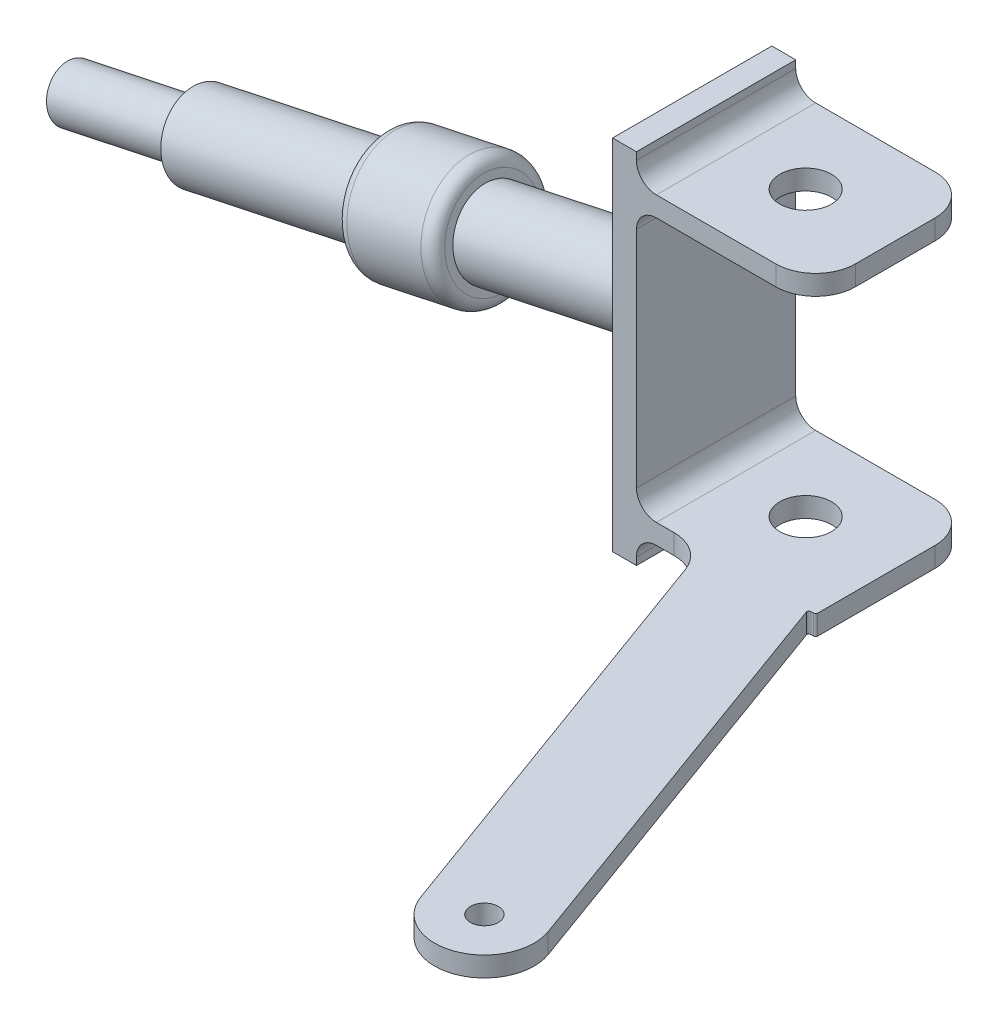
SolidWorks part; units mm, degrees
ref_plane "Front Plane" through (0, 0, 0) normal (0, 0, 1) x (1, 0, 0)
ref_plane "Top Plane" through (0, 0, 0) normal (0, 1, 0) x (1, 0, 0)
ref_plane "Right Plane" through (0, 0, 0) normal (1, 0, 0) x (0, 0, -1)
sketch "Sketch1" plane through (0, 0, 0) normal (1, 0, 0) x (0, 0, -1)
  line L1 (-20, 45) -> (20, 45)
  line L2 (-20, 45) -> (-20, -45)
  line L3 (-20, -45) -> (20, -45)
  line L4 (20, 45) -> (20, -45)
  line L5 (-20, 45) -> (20, -45) construction
  line L6 (-20, -45) -> (20, 45) construction
  point P0 (0, 0)
extrude "Boss-Extrude1" add sketch "Sketch1" along normal blind 6
sketch "Sketch2" plane through (6, 0, 0) normal (1, 0, 0) x (0, 0, -1)
  line L0 (20, -45) -> (20, 45) construction
  line L1 (-20, 33.1131) -> (20, 33.1131)
  line L2 (-20, 38.1131) -> (20, 38.1131)
  line L3 (-20, -33.1131) -> (20, -33.1131)
  line L4 (-20, -38.1131) -> (20, -38.1131)
  line L5 (-20, 33.1131) -> (20, -33.1131) construction
  line L6 (-20, -33.1131) -> (20, 33.1131) construction
  line L7 (-20, 38.1131) -> (-20, 33.1131)
  line L8 (20, 38.1131) -> (20, 33.1131)
  line L9 (20, -33.1131) -> (20, -38.1131)
  line L10 (-20, -38.1131) -> (-20, -33.1131)
  point P0 (0, 0)
extrude "Boss-Extrude2" add sketch "Sketch2" along normal blind 45
sketch "Sketch3" plane through (0, 38.1131, 0) normal (0, 1, 0) x (1, 0, 0)
  line L0 (6, 20) -> (51, -20) construction
  circle A0 centre (28.5, 0) radius 6.5
  dimension "D1" = 13
extrude "Cut-Extrude1" cut sketch "Sketch3" against normal through all
sketch "Sketch6" plane through (0, -33.1131, 0) normal (0, 1, 0) x (1, 0, 0)
  line L0 (28.5, 20) -> (28.5, -20) construction
  line L1 (51, 20) -> (6, 20) construction
  line L2 (51, -20) -> (6, -20) construction
  line L3 (6, -20) -> (51, -20)
  line L4 (22.4772, -20) -> (62.9266, -131.1338)
  line L5 (49.0816, -20) -> (86.4189, -122.5833)
  circle A0 centre (74.6727, -126.8585) radius 3.5
  arc A1 (62.9266, -131.1338) -> (86.4189, -122.5833) centre (74.6727, -126.8585) ccw
  line M3 (6, -20) -> (51, -20)
extrude "Boss-Extrude3" add sketch "Sketch6" against normal blind 5 contours L4 A1 L5 L3 A0 M3
sketch "Sketch7" plane through (0, 0, 0) normal (-1, 0, 0) x (0, 0, 1)
  line L0 (-20, 0) -> (20, 0) construction
  line L1 (-20, -45) -> (-20, 45) construction
  line L2 (20, 45) -> (20, -45) construction
ref_plane "Plane2" through (0, 0, 0) normal (0.9781, 0.2079, 0) x (0, 0, 1)
ref_plane "Plane3" through (0, 0, 0) normal (-0.2079, 0.9781, 0) x (0, 0, 1)
sketch "Sketch12" plane through (0, 0, 0) normal (0.9781, 0.2079, 0) x (0, 0, 1)
  circle A0 centre (0, 0) radius 10
  dimension "D1" = 20
sketch "Sketch16" plane through (0, 0, 0) normal (-0.2079, 0.9781, 0) x (0, 0, 1)
  line L0 (0, 0) -> (0, -126)
  line L1 (-20, 9.356) -> (20, 9.356) construction
  dimension "D1" = 126
sweep "Sweep3" add profiles "Sketch12" path "Sketch16"
ref_plane "Plane6" through (-49.8855, -10.6035, 0) normal (0.9781, 0.2079, 0) x (0, 0, 1)
sketch "Sketch19" plane through (-123.2466, -26.1969, 0) normal (-0.9781, -0.2079, 0) x (0, 0, 1)
  circle A0 centre (0, 0) radius 6.5
  dimension "D1" = 13
extrude "Boss-Extrude5" add sketch "Sketch19" along normal blind 33
sketch "Sketch20" plane through (-49.8855, -10.6035, 0) normal (0.9781, 0.2079, 0) x (0, 0, 1)
  circle A0 centre (0, 0) radius 15
  dimension "D1" = 30
extrude "Boss-Extrude6" add sketch "Sketch20" against normal blind 25
fillet "Fillet1" radius 10 1 edges at (51, 35.6131, -20)
fillet "Fillet2" radius 10 1 edges at (51, 35.6131, 20)
fillet "Fillet3" radius 10 3 edges at (51, -35.6131, -20)
fillet "Fillet4" radius 10 5 edges
fillet "Fillet5" radius 5 2 edges at (6, 38.1131, 0)
fillet "Fillet6" radius 5 2 edges at (6, 33.1131, 0)
fillet "Fillet7" radius 5 2 edges
fillet "Fillet8" radius 5 2 edges
fillet "Fillet9" radius 0.5 3 edges
fillet "Fillet10" radius 0.5 3 edges at (51, -35.6131, 20)
sketch "Sketch21" plane through (0, 0, 0) normal (-1, 0, 0) x (0, 0, 1)
  circle A0 centre (0, 0) radius 10
  dimension "D1" = 20
fillet "Fillet11" radius 3 2 edges at (-53.0042, 4.0687, 0) (-77.4579, -1.1291, 0)
sketch "Sketch24" plane through (0, 0, 0) normal (0.9781, 0.2079, 0) x (0, 0, 1)
  circle A0 centre (0, 0) radius 10
  dimension "D1" = 20
extrude "Boss-Extrude8" add sketch "Sketch24" along normal blind 3 contours A0
fillet "Fillet12" radius 3 1 edges at (0, 10.2234, 0)
